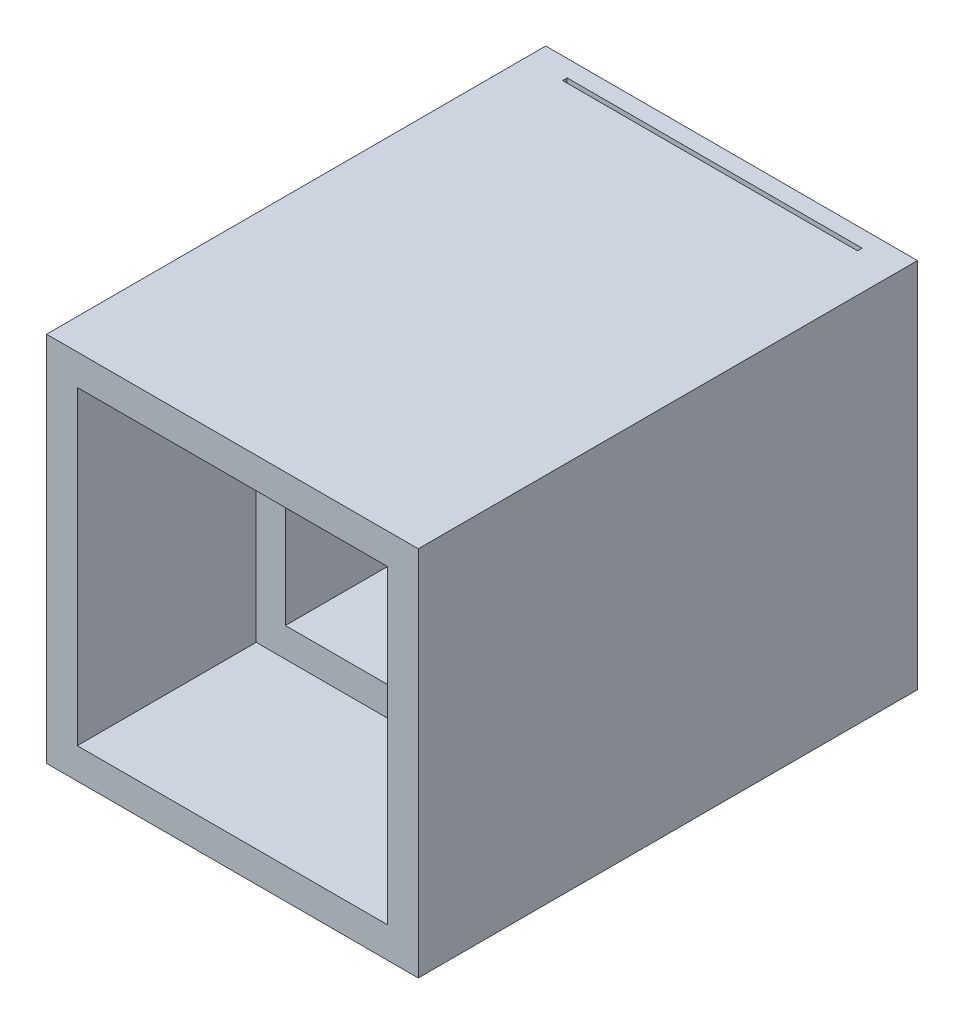
SolidWorks part; units mm, degrees
ref_plane "Front Plane" through (0, 0, 0) normal (0, 0, 1) x (1, 0, 0)
ref_plane "Top Plane" through (0, 0, 0) normal (0, 1, 0) x (1, 0, 0)
ref_plane "Right Plane" through (0, 0, 0) normal (1, 0, 0) x (0, 0, -1)
sketch "Sketch1" plane through (0, 0, 0) normal (0, 0, 1) x (1, 0, 0)
  line L0 (-30.734, 30.734) -> (30.734, 30.734)
  line L1 (-20.828, 20.828) -> (20.828, 20.828)
  line L2 (-20.828, 20.828) -> (-20.828, -20.828)
  line L3 (-20.828, -20.828) -> (20.828, -20.828)
  line L4 (20.828, 20.828) -> (20.828, -20.828)
  line L5 (-20.828, 20.828) -> (20.828, -20.828) construction
  line L6 (-20.828, -20.828) -> (20.828, 20.828) construction
  line L7 (30.734, 30.734) -> (30.734, -30.734)
  line L8 (-30.734, -30.734) -> (30.734, -30.734)
  line L9 (-30.734, 30.734) -> (-30.734, -30.734)
  point P0 (0, 0)
  dimension "D1" = 41.656
  dimension "D2" = 9.906
extrude "Boss-Extrude1" add sketch "Sketch1" along normal blind 76.2 and the other way blind 6.35 contours L0 L7 L8 L9
extrude "Cut-Extrude1" cut sketch "Sketch1<3>" along normal through all contours L1 L4 L3 L2
sketch "Sketch1<3>" plane through (0, 0, 0) normal (0, 0, 1) x (1, 0, 0) same geometry as "Sketch1"
sketch "Sketch3" plane through (0, 30.734, 0) normal (0, 1, 0) x (1, 0, 0)
  line L0 (-30.734, 6.35) -> (-30.734, -76.2) construction
  line L1 (30.734, 6.35) -> (30.734, -76.2) construction
  line L2 (-30.734, 6.35) -> (-30.734, 0) construction
  line L3 (-30.734, 0) -> (30.734, 0) construction
  point P0 (-30.734, 3.175)
  point P1 (30.734, 3.175)
  point P11 (-30.734, 3.175)
ref_plane "Plane1" through (0, 0, -3.175) normal (0, 0, 1) x (1, 0, 0)
ref_plane "Plane2" through (0, 0, 46.609) normal (0, 0, 1) x (1, 0, 0)
sketch "Sketch2" plane through (0, 0, 46.609) normal (0, 0, 1) x (1, 0, 0)
  line L0 (30.734, 30.734) -> (30.734, -30.734) construction
  line L1 (-25.654, 25.654) -> (25.654, 25.654)
  line L2 (-25.654, 25.654) -> (-25.654, -25.654)
  line L3 (-25.654, -25.654) -> (25.654, -25.654)
  line L4 (25.654, 25.654) -> (25.654, -25.654)
  line L5 (-25.654, 25.654) -> (25.654, -25.654) construction
  line L6 (-25.654, -25.654) -> (25.654, 25.654) construction
  point P0 (0, 0)
  dimension "D1" = 5.08
extrude "Cut-Extrude2" cut sketch "Sketch2" along normal through all
sketch "Sketch5" plane through (0, 0, -6.35) normal (0, 0, -1) x (-1, 0, 0)
  line L1 (-4.572, 4.572) -> (4.572, 4.572)
  line L2 (-4.572, 4.572) -> (-4.572, -4.572)
  line L3 (-4.572, -4.572) -> (4.572, -4.572)
  line L4 (4.572, 4.572) -> (4.572, -4.572)
  line L5 (-4.572, 4.572) -> (4.572, -4.572) construction
  line L6 (-4.572, -4.572) -> (4.572, 4.572) construction
  point P0 (0, 0)
  dimension "D1" = 9.144
extrude "Cut-Extrude3" cut sketch "Sketch5" against normal through all
sketch "Sketch6" plane through (0, 30.734, 0) normal (0, 1, 0) x (1, 0, 0)
  line L0 (-33.8074, 3.175) -> (33.8074, 3.175) construction
  line L1 (-24.384, 3.556) -> (24.384, 3.556)
  line L2 (-24.384, 3.556) -> (-24.384, 2.794)
  line L3 (-24.384, 2.794) -> (24.384, 2.794)
  line L4 (24.384, 3.556) -> (24.384, 2.794)
  line L5 (-24.384, 3.556) -> (24.384, 2.794) construction
  line L6 (-24.384, 2.794) -> (24.384, 3.556) construction
  line L7 (30.734, 6.35) -> (30.734, -76.2) construction
  point P0 (0, 3.175)
  dimension "D1" = 6.35
  dimension "D2" = 0.762
extrude "Cut-Extrude4" cut sketch "Sketch6" against normal offset from surface (55.118 mm away) 6.35 up to face at (0, -30.734, 34.925)
